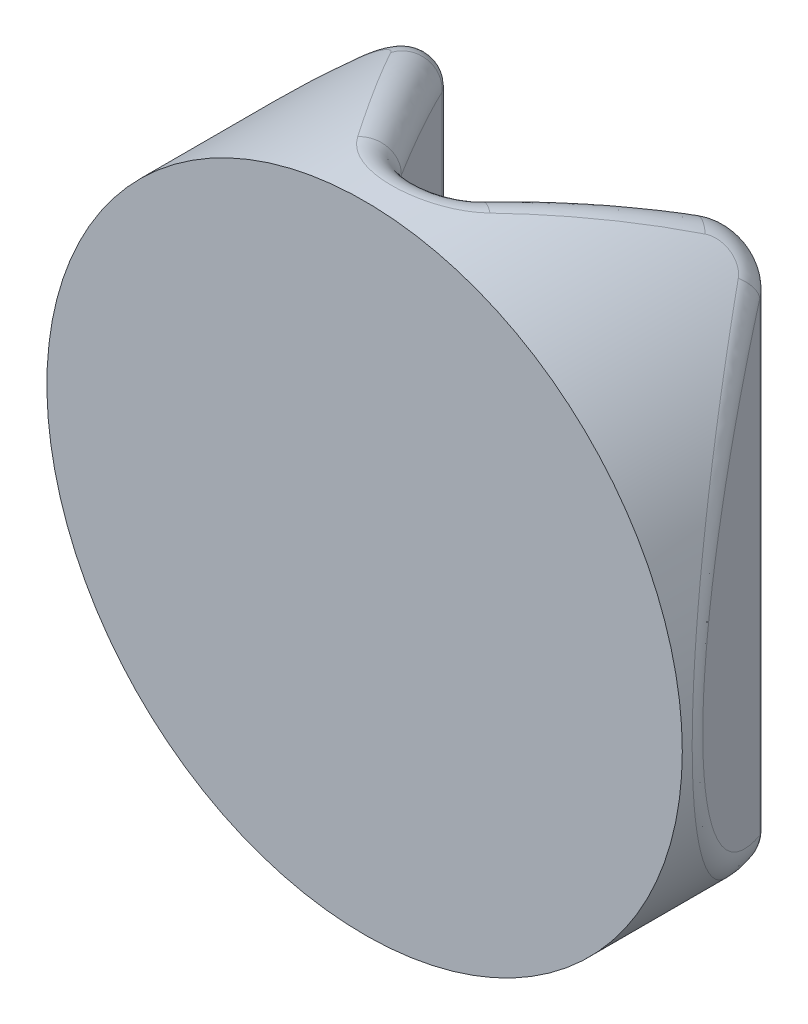
SolidWorks part; units mm, degrees
ref_plane "Plan de face" through (0, 0, 0) normal (0, 0, 1) x (1, 0, 0)
ref_plane "Plan de dessus" through (0, 0, 0) normal (0, 1, 0) x (1, 0, 0)
ref_plane "Plan de droite" through (0, 0, 0) normal (1, 0, 0) x (0, 0, -1)
sketch "Esquisse1" plane through (0, 0, 0) normal (0, 0, 1) x (1, 0, 0)
  circle A0 centre (0, 0) radius 34.9
  dimension "D1" = 69.8
extrude "Boss.-Extru.1" add sketch "Esquisse1" along normal blind 28
sketch "Esquisse2" plane through (0, 0, 0) normal (0, 1, 0) x (1, 0, 0)
  line L0 (0, 0) -> (0, -50000) construction
  line L1 (-34.9, -28) -> (34.9, -28) construction
  line L2 (-17.45, 0) -> (0, -26)
  line L3 (34.9, 0) -> (-34.9, 0) construction
  line L4 (-34.9, -26) -> (-17.45, 0)
  line L5 (-34.9, -1026) -> (-34.9, 48974) construction
  line L6 (-34.9, 0) -> (-34.9, -28) construction
  line L7 (17.45, 0) -> (0, -26)
  line L8 (34.9, -26) -> (17.45, 0)
  line L9 (-34.9, -26) -> (-34.9, 0)
  line L10 (-34.9, 0) -> (34.9, 0)
  line L11 (34.9, 0) -> (34.9, -26)
  point P5 (0, -28)
  point P7 (0, -26)
  point P10 (-17.45, 0)
  point P11 (-34.9, -26)
  dimension "D1" = 2
  dimension "D2" = 2
  dimension "D3" = 17.45
extrude "Enlèv. mat.-Extru.1" cut sketch "Esquisse2" against normal through all both and the other way through all contours L10 L9 L4 | L10 L2 L7 | L11 L10 L8 region at (0, 0, 8.6667) region at (-29.0833, 0, 8.6667) region at (29.0833, 0, 8.6667)
fillet "Congé1" radius 5 2 edges at (17.45, 0, 0) (-17.45, 0, 0)
fillet "Congé2" radius 5 1 edges at (0, 0, 26)
fillet "Congé3" radius 3 12 edges at (16.7896, 30.5961, 4.016) (8.8061, 33.7707, 12.8791) (-17.4943, 30.1987, 3.9724) (-0.1684, 34.8996, 22.025) (-8.8061, 33.7707, 12.8791) (17.4943, -30.1987, 3.9724) (0.1684, -34.8996, 22.025) (-16.7896, -30.5961, 4.016) (-8.8061, -33.7707, 12.8791) (8.8061, -33.7707, 12.8791) (34.9, 0, 26) (-34.9, 0, 26)
